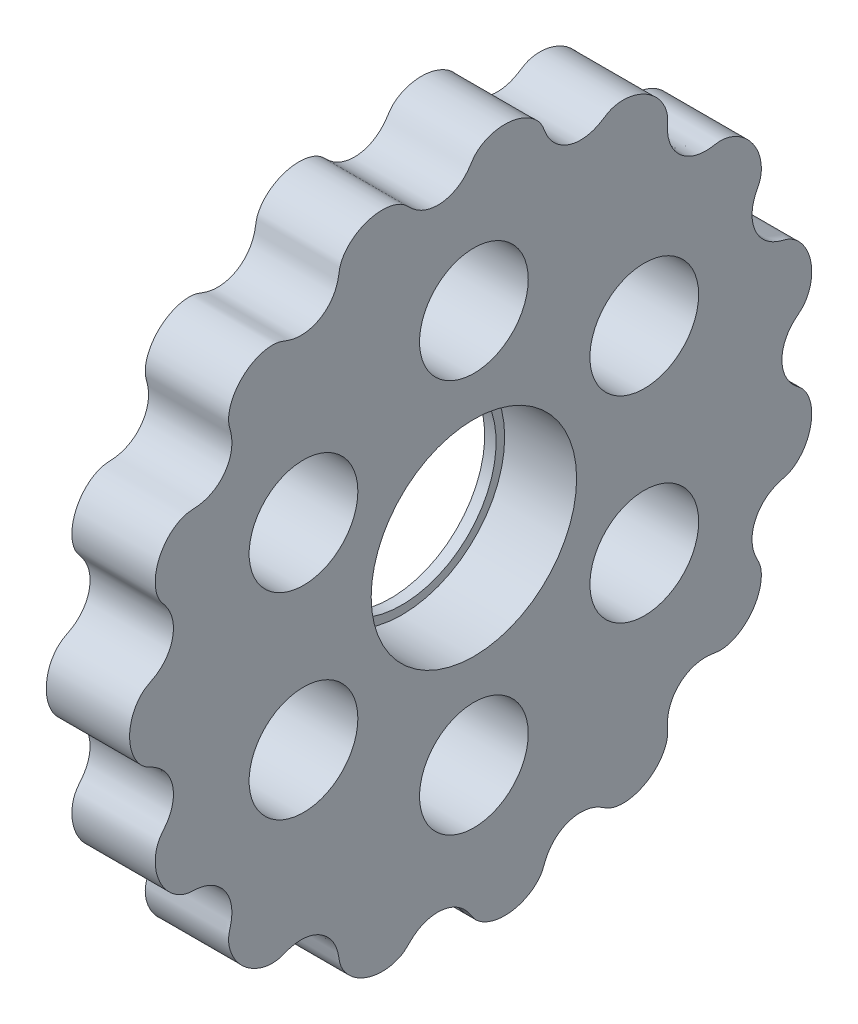
SolidWorks part; units mm, degrees
ref_plane "Front Plane" through (0, 0, 0) normal (0, 0, 1) x (1, 0, 0)
ref_plane "Top Plane" through (0, 0, 0) normal (0, 1, 0) x (1, 0, 0)
ref_plane "Right Plane" through (0, 0, 0) normal (1, 0, 0) x (0, 0, -1)
sketch "Sketch2" plane through (0, 0, 0) normal (0, 0, 1) x (1, 0, 0)
  line L0 (0, 0) -> (58.591, 0) construction
  line L2 (0, 0) -> (18.4, 0)
  line L3 (0, 0) -> (0, 2.5)
  line L4 (0, 2.5) -> (18.4, 2.5)
  line L5 (18.4, 0) -> (18.4, 2.5)
  line L6 (6.0094, 2.5) -> (6.0094, 6)
  line L11 (6.0094, 6) -> (9.9794, 6)
  line L16 (12.9794, 6) -> (12.9794, 3)
  line L17 (12.9794, 3) -> (13.6398, 3)
  line L18 (13.6398, 3) -> (13.6398, 2.5)
  line L19 (13.6398, 2.5) -> (6.0094, 2.5)
  line L22 (13.6398, 2.5) -> (16.1198, 2.5)
  line L23 (13.6398, 2.5) -> (13.6398, 4)
  line L24 (13.6398, 4) -> (16.1198, 4)
  line L25 (16.1198, 2.5) -> (16.1198, 4)
  line L27 (6.0094, 6) -> (9.9794, 6)
  line L28 (6.0094, 6) -> (6.0094, 9)
  line L29 (6.0094, 9) -> (9.9794, 9)
  line L30 (9.9794, 6) -> (9.9794, 9)
  line L31 (6.0094, 9) -> (6.0094, 8.25)
  line L32 (6.0094, 8.25) -> (5.0094, 8.25)
  line L33 (8.6609, 22.001) -> (8.6609, 12.476) construction
  line L34 (5.0094, 12.476) -> (12.3124, 12.476)
  line L35 (9.9794, 9) -> (12.3124, 9)
  line L36 (5.0094, 7.9375) -> (1.8344, 7.9375)
  line L37 (5.0094, 8.25) -> (5.0094, 12.476)
  line L38 (5.0094, 7.9375) -> (5.0094, 13.9365)
  line L39 (5.0094, 13.9365) -> (1.8344, 13.9365)
  line L40 (1.8344, 7.9375) -> (1.8344, 13.9365)
  line L41 (5.0094, 22.001) -> (12.3124, 22.001)
  line L42 (5.0094, 22.001) -> (5.0094, 30.1625)
  line L43 (5.0094, 30.1625) -> (12.3124, 30.1625)
  line L44 (12.3124, 22.001) -> (12.3124, 30.1625)
  line L49 (16.6398, 22.001) -> (16.6398, 7.5)
  line L51 (23.0198, 7.5) -> (23.0198, 6.5)
  line L54 (16.1198, 4) -> (13.6398, 4)
  line L56 (18.0398, 7.5) -> (23.0198, 7.5)
  line L57 (13.3124, 22.001) -> (16.6398, 22.001)
  line L58 (16.1198, 3.5) -> (20.0198, 3.5)
  line L59 (29.9098, 14) -> (26.9098, 11)
  line L60 (4.0094, 31.75) -> (18.0398, 31.75)
  line L61 (18.0398, 7.5) -> (23.0198, 7.5)
  line L62 (18.0398, 7.5) -> (18.0398, 12)
  line L63 (18.0398, 12) -> (23.0198, 12)
  line L64 (23.0198, 7.5) -> (23.0198, 12)
  line L65 (18.0398, 31.75) -> (18.0398, 12)
  line L66 (23.0198, 11) -> (26.9098, 11)
  line L67 (34.8098, 23) -> (31.3098, 19.5)
  line L68 (35.8098, 31) -> (38.7998, 33.99)
  line L69 (29.9098, 14) -> (29.9098, 15)
  line L70 (29.9098, 15) -> (22.9398, 15)
  line L71 (22.9398, 15) -> (21.0398, 15)
  line L72 (18.0398, 7.5) -> (16.6398, 7.5)
  line L73 (21.0398, 15) -> (21.0398, 43)
  line L74 (19.5798, 40) -> (9.6198, 40)
  line L75 (9.6198, 40) -> (4.0094, 40)
  line L76 (21.0398, 43) -> (19.5798, 43)
  line L77 (22.9398, 15) -> (29.9098, 15)
  line L78 (22.9398, 15) -> (22.9398, 21)
  line L79 (22.9398, 21) -> (29.9098, 21)
  line L80 (29.9098, 15) -> (29.9098, 21)
  line L81 (9.6198, 40) -> (19.5798, 40)
  line L82 (9.6198, 40) -> (9.6198, 50)
  line L83 (9.6198, 50) -> (19.5798, 50)
  line L84 (19.5798, 40) -> (19.5798, 50)
  line L85 (4.0094, 40) -> (4.0094, 31.75)
  line L86 (12.9794, 3) -> (12.9794, 2.5)
  line L87 (31.3098, 19.5) -> (29.9098, 19.5)
  line L88 (21.4694, 63.5) -> (21.4694, 51.308)
  line L89 (21.4694, 63.5) -> (25.9398, 63.5)
  line L90 (25.9398, 63.5) -> (25.9398, 25)
  line L91 (27.8398, 25) -> (25.9398, 25)
  line L92 (9.6198, 48) -> (8.1598, 48)
  line L93 (8.1598, 48) -> (8.1598, 53.476)
  line L94 (8.1598, 53.476) -> (19.5798, 53.476)
  line L95 (19.5798, 53.476) -> (19.5798, 50)
  line L96 (13.8698, 63.001) -> (13.8698, 53.476) construction
  line L97 (8.1598, 63.001) -> (19.5798, 63.001)
  line L98 (8.1598, 63.001) -> (8.1598, 68.2625)
  line L99 (8.1598, 68.2625) -> (19.5798, 68.2625)
  line L100 (19.5798, 63.001) -> (19.5798, 68.2625)
  line L101 (12.9794, 6) -> (11.9794, 6)
  line L102 (8.1598, 44.825) -> (4.9848, 44.825)
  line L103 (8.1598, 44.825) -> (8.1598, 54.9365)
  line L104 (8.1598, 54.9365) -> (4.9848, 54.9365)
  line L106 (9.9794, 6) -> (10.8794, 6)
  line L107 (27.8398, 25) -> (34.8098, 25)
  line L108 (34.8098, 25) -> (34.8098, 23)
  line L109 (0, 0) -> (-2, 0)
  line L110 (0, 0) -> (0, 11)
  line L111 (27.8398, 25) -> (34.8098, 25)
  line L112 (27.8398, 25) -> (27.8398, 32.5)
  line L113 (27.8398, 32.5) -> (34.8098, 32.5)
  line L114 (34.8098, 25) -> (34.8098, 32.5)
  line L115 (35.8098, 31) -> (34.8098, 31)
  line L116 (27.8398, 32.5) -> (27.8398, 64.5)
  line L117 (20.5373, 74.025) -> (6.2023, 74.025)
  line L118 (6.2023, 74.025) -> (6.2023, 76.2)
  line L119 (38.7998, 47.29) -> (30.8398, 55.25)
  line L120 (0, 11) -> (-2, 11)
  line L121 (38.7998, 43.815) -> (30.8623, 43.815)
  line L123 (-4.8152, 69.85) -> (1.5348, 76.2)
  line L124 (38.7998, 47.29) -> (38.7998, 33.99)
  line L125 (-2, 0) -> (-2, 11)
  line L126 (38.7998, 37.465) -> (30.8623, 37.465)
  line L127 (30.8623, 43.815) -> (30.8623, 37.465)
  line L128 (6.0094, 2.5) -> (6.0094, 0)
  line L129 (-0.0152, 63.5) -> (-0.0152, 30)
  line L132 (4.9848, 63.5) -> (-0.0152, 63.5)
  line L136 (-1.8152, 30) -> (-11.7752, 30)
  line L138 (-13.7752, 25.4) -> (-2, 25.4)
  line L139 (-2, 25.4) -> (-2, 11.5)
  line L140 (27.8398, 64.5) -> (20.5373, 64.5)
  line L141 (-1.8152, 30) -> (-11.7752, 30)
  line L142 (-1.8152, 30) -> (-1.8152, 39)
  line L143 (-1.8152, 39) -> (-11.7752, 39)
  line L144 (-11.7752, 30) -> (-11.7752, 39)
  line L145 (20.5373, 64.5) -> (20.5373, 74.025)
  line L146 (-12.7752, 37) -> (-12.7752, 47.29)
  line L147 (-12.7752, 37) -> (-11.7752, 37)
  line L148 (30.8398, 55.25) -> (30.8398, 76.2)
  line L149 (11.9794, 6) -> (11.9794, 5.45)
  line L154 (-2, 11.5) -> (0.5, 11.5)
  line L155 (4.9848, 60.6197) -> (24.0348, 60.6197)
  line L160 (4.9848, 60.6197) -> (4.9848, 55.8572)
  line L161 (4.9848, 55.8572) -> (24.0348, 55.8572)
  line L166 (24.0348, 60.6197) -> (24.0348, 55.8572)
  line L167 (4.9848, 60.6197) -> (24.0348, 55.8572) construction
  line L172 (4.9848, 55.8572) -> (24.0348, 60.6197) construction
  line L173 (24.0348, 62.2072) -> (25.9398, 62.2072)
  line L174 (11.9794, 5.45) -> (10.8794, 5.45)
  line L175 (10.8794, 6) -> (10.8794, 5.45)
  line L176 (24.0348, 62.2072) -> (24.0348, 54.2697)
  line L177 (24.0348, 54.2697) -> (25.9398, 54.2697)
  line L178 (25.9398, 62.2072) -> (25.9398, 54.2697)
  line L179 (24.0348, 62.2072) -> (25.9398, 54.2697) construction
  line L180 (24.0348, 54.2697) -> (25.9398, 62.2072) construction
  line L181 (3, 19.6197) -> (15.7, 19.6197)
  line L182 (3, 19.6197) -> (3, 14.8572)
  line L183 (3, 14.8572) -> (15.7, 14.8572)
  line L184 (15.7, 19.6197) -> (15.7, 14.8572)
  line L185 (3, 19.6197) -> (15.7, 14.8572) construction
  line L186 (3, 14.8572) -> (15.7, 19.6197) construction
  line L187 (15.7, 21.2072) -> (16.6398, 21.2072)
  line L188 (15.7, 21.2072) -> (15.7, 13.2697)
  line L189 (15.7, 13.2697) -> (16.6398, 13.2697)
  line L190 (16.6398, 21.2072) -> (16.6398, 13.2697)
  line L191 (15.7, 21.2072) -> (16.6398, 13.2697) construction
  line L192 (15.7, 13.2697) -> (16.6398, 21.2072) construction
  line L193 (0.5, 11.5) -> (0.5, 6.9375)
  line L194 (0.5, 6.9375) -> (1.8344, 6.9375)
  line L195 (23.0198, 6.5) -> (20.0198, 3.5)
  line L196 (4.9848, 63.5) -> (4.9848, 54.9365)
  line L197 (3, 43.825) -> (4.9848, 43.825)
  line L198 (1.8344, 6.9375) -> (1.8344, 7.9375)
  line L199 (6.0094, 0) -> (12.9794, 0)
  line L200 (12.9794, 0) -> (12.9794, 2.5)
  line L201 (18.0398, 31.75) -> (18.0398, 35.875)
  line L202 (18.0398, 35.875) -> (21.0398, 35.875)
  line L203 (30.8398, 76.2) -> (6.2023, 76.2)
  line L204 (2.7573, 69.85) -> (7.2023, 69.85) construction
  line L205 (7.2023, 67.4688) -> (26.2523, 67.4688)
  line L206 (7.2023, 74.025) -> (7.2023, 64.5)
  line L207 (7.2023, 64.5) -> (-1.8152, 64.5)
  line L208 (-1.8152, 64.5) -> (-1.8152, 39)
  line L209 (-12.7752, 47.29) -> (-4.8152, 55.25)
  line L210 (-4.8152, 55.25) -> (-4.8152, 69.85)
  line L211 (7.2023, 67.4688) -> (7.2023, 72.2312)
  line L212 (7.2023, 72.2312) -> (26.2523, 72.2313)
  line L213 (26.2523, 67.4688) -> (26.2523, 72.2313)
  line L214 (26.2523, 73.8187) -> (30.8398, 73.8187)
  line L215 (26.2523, 73.8187) -> (26.2523, 65.8813)
  line L216 (26.2523, 65.8813) -> (30.8398, 65.8813)
  line L217 (30.8398, 73.8187) -> (30.8398, 65.8813)
  line L218 (2.7573, 72.2313) -> (24.9823, 72.2313)
  line L219 (2.7573, 72.2313) -> (2.7573, 67.4687)
  line L220 (2.7573, 67.4687) -> (24.9823, 67.4687)
  line L221 (24.9823, 72.2313) -> (24.9823, 67.4687)
  line L222 (24.9823, 69.85) -> (20.5373, 69.85) construction
  line L223 (21.4694, 51.308) -> (22.9398, 51.308)
  line L224 (22.9398, 51.308) -> (22.9398, 21)
  line L225 (13.6398, 4) -> (13.6398, 12.2697)
  line L226 (13.6398, 12.2697) -> (13.3124, 12.2697)
  line L227 (13.3124, 12.2697) -> (13.3124, 22.001)
  line L228 (12.3124, 9) -> (12.3124, 12.476)
  line L229 (-1.8152, 30) -> (-0.0152, 30)
  line L230 (8.1598, 65.6317) -> (2.7573, 65.6317) construction
  line L231 (19.5798, 65.6317) -> (24.9823, 65.6317) construction
  line L232 (1.5348, 76.2) -> (6.2023, 76.2)
  line L233 (-11.7752, 30) -> (-13.7752, 30)
  line L234 (-13.7752, 30) -> (-13.7752, 25.4)
  line L235 (3, 13.9365) -> (3, 43.825)
  line L236 (4.9848, 54.9365) -> (4.9848, 44.825)
  line L237 (4.9848, 43.825) -> (4.9848, 44.825)
  circle A0 centre (26.8898, 25.95) radius 0.95
  circle A1 centre (21.9898, 15.95) radius 0.95
  circle A2 centre (17.3398, 8.2) radius 0.7
  circle A3 centre (10.4294, 6.45) radius 0.45
  circle A4 centre (-0.9152, 30.9) radius 0.9
  point P7 (24.9873, 58.2385)
  point P131 (16.1699, 17.2385)
  point P135 (14.5098, 58.2385)
  point P146 (9.35, 17.2385)
sketch "Sketch3" plane through (0, 0, 0) normal (1, 0, 0) x (0, 0, -1)
  line L0 (0, 0) -> (0, 69.85) construction
  line L1 (0, 0) -> (13.6271, 68.5079) construction
  line L2 (0, 0) -> (0, 58.2385) construction
  line L3 (0, 0) -> (50.436, 29.1192) construction
  line L4 (0, 0) -> (0, 31.75) construction
  line L5 (0, 0) -> (12.1502, 29.3332) construction
  line L6 (0, 0) -> (0, 17.2385) construction
  line L7 (0, 0) -> (14.929, 8.6192) construction
  line L8 (0, 0) -> (0, 58.2385) construction
  line L9 (0, 0) -> (50.436, 29.1192) construction
  line L10 (0, 0) -> (5.9583, 29.9542) construction
  line L11 (0, 0) -> (16.9677, 25.394) construction
  circle A0 centre (0, 0) radius 69.85 construction
  circle A1 centre (0, 0) radius 58.2385 construction
  circle A2 centre (0, 0) radius 31.75 construction
  circle A3 centre (0, 0) radius 17.2385 construction
  circle A4 centre (0, 69.85) radius 3.175
  circle A5 centre (0, 58.2385) radius 4.7625
  circle A6 centre (0, 31.75) radius 3.175
  circle A7 centre (0, 17.2385) radius 4.7625
  circle A8 centre (13.6271, 68.5079) radius 3.175
  circle A9 centre (26.7304, 64.533) radius 3.175
  circle A10 centre (38.8066, 58.0782) radius 3.175
  circle A11 centre (49.3914, 49.3914) radius 3.175
  circle A12 centre (58.0782, 38.8066) radius 3.175
  circle A13 centre (64.533, 26.7304) radius 3.175
  circle A14 centre (68.5079, 13.6271) radius 3.175
  circle A15 centre (69.85, 0) radius 3.175
  circle A16 centre (68.5079, -13.6271) radius 3.175
  circle A17 centre (64.533, -26.7304) radius 3.175
  circle A18 centre (58.0782, -38.8066) radius 3.175
  circle A19 centre (49.3914, -49.3914) radius 3.175
  circle A20 centre (38.8066, -58.0782) radius 3.175
  circle A21 centre (26.7304, -64.533) radius 3.175
  circle A22 centre (13.6271, -68.5079) radius 3.175
  circle A23 centre (0, -69.85) radius 3.175
  circle A24 centre (-13.6271, -68.5079) radius 3.175
  circle A25 centre (-26.7304, -64.533) radius 3.175
  circle A26 centre (-38.8066, -58.0782) radius 3.175
  circle A27 centre (-49.3914, -49.3914) radius 3.175
  circle A28 centre (-58.0782, -38.8066) radius 3.175
  circle A29 centre (-64.533, -26.7304) radius 3.175
  circle A30 centre (-68.5079, -13.6271) radius 3.175
  circle A31 centre (-69.85, 0) radius 3.175
  circle A32 centre (-68.5079, 13.6271) radius 3.175
  circle A33 centre (-64.533, 26.7304) radius 3.175
  circle A34 centre (-58.0782, 38.8066) radius 3.175
  circle A35 centre (-49.3914, 49.3914) radius 3.175
  circle A36 centre (-38.8066, 58.0782) radius 3.175
  circle A37 centre (-26.7304, 64.533) radius 3.175
  circle A38 centre (-13.6271, 68.5079) radius 3.175
  circle A47 centre (50.436, 29.1192) radius 4.7625
  circle A48 centre (50.436, -29.1192) radius 4.7625
  circle A49 centre (0, -58.2385) radius 4.7625
  circle A50 centre (-50.436, -29.1192) radius 4.7625
  circle A51 centre (-50.436, 29.1192) radius 4.7625
  circle A58 centre (12.1502, 29.3332) radius 3.175
  circle A59 centre (22.4506, 22.4506) radius 3.175
  circle A60 centre (29.3332, 12.1502) radius 3.175
  circle A61 centre (31.75, 0) radius 3.175
  circle A62 centre (29.3332, -12.1502) radius 3.175
  circle A63 centre (22.4506, -22.4506) radius 3.175
  circle A64 centre (12.1502, -29.3332) radius 3.175
  circle A65 centre (0, -31.75) radius 3.175
  circle A66 centre (-12.1502, -29.3332) radius 3.175
  circle A67 centre (-22.4506, -22.4506) radius 3.175
  circle A68 centre (-29.3332, -12.1502) radius 3.175
  circle A69 centre (-31.75, 0) radius 3.175
  circle A70 centre (-29.3332, 12.1502) radius 3.175
  circle A71 centre (-22.4506, 22.4506) radius 3.175
  circle A72 centre (14.929, 8.6192) radius 4.7625
  circle A73 centre (14.929, -8.6192) radius 4.7625
  circle A74 centre (0, -17.2385) radius 4.7625
  circle A75 centre (-14.929, -8.6192) radius 4.7625
  circle A76 centre (-14.929, 8.6192) radius 4.7625
  circle A77 centre (0, 0) radius 50
  circle A78 centre (0, 0) radius 9
  circle A79 centre (-12.1502, 29.3332) radius 3.175
  circle A80 centre (0, 0) radius 76.2
  circle A81 centre (0, 0) radius 74.025
  circle A82 centre (0, 69.85) radius 3.9687
  circle A83 centre (49.3914, 49.3914) radius 3.9687
  circle A84 centre (69.85, 0) radius 3.9688
  circle A85 centre (49.3914, -49.3914) radius 3.9687
  circle A86 centre (0, -69.85) radius 3.9687
  circle A87 centre (-49.3914, -49.3914) radius 3.9687
  circle A88 centre (-69.85, 0) radius 3.9688
  circle A89 centre (-49.3914, 49.3914) radius 3.9687
  circle A90 centre (0, 69.85) radius 2.3812
  circle A91 centre (13.6271, 68.5079) radius 2.3812
  circle A92 centre (26.7304, 64.533) radius 2.3813
  circle A93 centre (38.8066, 58.0782) radius 2.3812
  circle A94 centre (49.3914, 49.3914) radius 2.3812
  circle A95 centre (58.0782, 38.8066) radius 2.3812
  circle A96 centre (64.533, 26.7304) radius 2.3813
  circle A97 centre (68.5079, 13.6271) radius 2.3813
  circle A98 centre (69.85, 0) radius 2.3813
  circle A99 centre (68.5079, -13.6271) radius 2.3813
  circle A100 centre (64.533, -26.7304) radius 2.3813
  circle A101 centre (58.0782, -38.8066) radius 2.3812
  circle A102 centre (49.3914, -49.3914) radius 2.3812
  circle A103 centre (38.8066, -58.0782) radius 2.3812
  circle A104 centre (26.7304, -64.533) radius 2.3813
  circle A105 centre (13.6271, -68.5079) radius 2.3812
  circle A106 centre (0, -69.85) radius 2.3812
  circle A107 centre (-13.6271, -68.5079) radius 2.3812
  circle A108 centre (-26.7304, -64.533) radius 2.3813
  circle A109 centre (-38.8066, -58.0782) radius 2.3812
  circle A110 centre (-49.3914, -49.3914) radius 2.3812
  circle A111 centre (-58.0782, -38.8066) radius 2.3812
  circle A112 centre (-64.533, -26.7304) radius 2.3812
  arc A113 (3.0399, 30.8338) -> (8.9911, 29.65) centre (5.9583, 29.9542) cw
  arc A114 (14.6081, 27.3234) -> (19.6532, 23.9523) centre (16.9677, 25.394) cw
  arc A115 (23.9523, 19.6532) -> (27.3234, 14.6081) centre (25.394, 16.9677) cw
  arc A116 (29.65, 8.9911) -> (30.8338, 3.0399) centre (29.9542, 5.9583) cw
  arc A117 (30.8338, -3.0399) -> (29.65, -8.9911) centre (29.9542, -5.9583) cw
  arc A118 (27.3234, -14.6081) -> (23.9523, -19.6532) centre (25.394, -16.9677) cw
  arc A119 (19.6532, -23.9523) -> (14.6081, -27.3234) centre (16.9677, -25.394) cw
  arc A120 (8.9911, -29.65) -> (3.0399, -30.8338) centre (5.9583, -29.9542) cw
  arc A121 (-3.0399, -30.8338) -> (-8.9911, -29.65) centre (-5.9583, -29.9542) cw
  arc A122 (-14.6081, -27.3234) -> (-19.6532, -23.9523) centre (-16.9677, -25.394) cw
  arc A123 (-23.9523, -19.6532) -> (-27.3234, -14.6081) centre (-25.394, -16.9677) cw
  arc A124 (-29.65, -8.9911) -> (-30.8338, -3.0399) centre (-29.9542, -5.9583) cw
  arc A125 (-30.8338, 3.0399) -> (-29.65, 8.9911) centre (-29.9542, 5.9583) cw
  arc A126 (-27.3234, 14.6081) -> (-23.9523, 19.6532) centre (-25.394, 16.9677) cw
  arc A127 (-19.6532, 23.9523) -> (-14.6081, 27.3234) centre (-16.9677, 25.394) cw
  arc A128 (-8.9911, 29.65) -> (-3.0399, 30.8338) centre (-5.9583, 29.9542) cw
  arc A129 (26.9875, 0) -> (26.9932, 0.1932) centre (30.2705, 0) cw
  arc A130 (65.0988, 0.2771) -> (65.0875, 0) centre (68.4964, 0) ccw
  circle A131 centre (1.5875, 0) radius 40
  circle A132 centre (1.5875, 0) radius 2.5
  circle A133 centre (1.5875, 0) radius 3
  circle A134 centre (1.5875, 0) radius 43
  circle A135 centre (-68.5079, -13.6271) radius 2.3813
  circle A136 centre (-69.85, 0) radius 2.3813
  circle A137 centre (-68.5079, 13.6271) radius 2.3813
  circle A138 centre (-64.533, 26.7304) radius 2.3812
  circle A139 centre (-58.0782, 38.8066) radius 2.3812
  circle A140 centre (-49.3914, 49.3914) radius 2.3812
  circle A141 centre (-38.8066, 58.0782) radius 2.3812
  circle A142 centre (-26.7304, 64.533) radius 2.3813
  circle A143 centre (-13.6271, 68.5079) radius 2.3812
  circle A144 centre (0, 58.2385) radius 2.3812
  circle A145 centre (0, 58.2385) radius 3.9688
  circle A146 centre (50.436, 29.1192) radius 3.9688
  circle A147 centre (50.436, 29.1192) radius 2.3813
  circle A148 centre (50.436, -29.1192) radius 3.9687
  circle A149 centre (50.436, -29.1192) radius 2.3812
  circle A150 centre (0, -58.2385) radius 3.9687
  circle A151 centre (0, -58.2385) radius 2.3812
  circle A152 centre (-50.436, -29.1192) radius 3.9687
  circle A153 centre (-50.436, -29.1192) radius 2.3812
  circle A154 centre (-50.436, 29.1192) radius 3.9687
  circle A155 centre (-50.436, 29.1192) radius 2.3812
  spline S1 degree 4 number of poles 499 (26.9875, 0) -> (26.9932, 0.1932)
  spline S3 degree 4 number of poles 617 (65.0875, 0) -> (65.0988, 0.2771)
  point P116 (0, 0)
  point P225 (0, 0)
sketch "Sketch4" plane through (0, 0, 0) normal (0, 0, 1) x (1, 0, 0)
  line L0 (6.0094, 9) -> (9.9794, 9) construction
  line L1 (9.9794, 9) -> (12.3124, 9) construction
  line L2 (12.3124, 9) -> (12.3124, 12.476) construction
  line L3 (6.0094, 9) -> (9.9794, 9)
  line L4 (6.0094, 6) -> (6.0094, 9) construction
  line L7 (5.0094, 12.476) -> (12.3124, 12.476) construction
  line L8 (5.0094, 8.25) -> (5.0094, 12.476) construction
  line L9 (6.0094, 8.25) -> (5.0094, 8.25) construction
  line L14 (6.0094, 8.25) -> (6.0094, 9)
  line L17 (5.0094, 12.476) -> (12.3124, 12.476)
  line L18 (5.0094, 8.25) -> (5.0094, 12.476)
  line L19 (6.0094, 8.25) -> (5.0094, 8.25)
  line L20 (9.9794, 9) -> (12.3124, 9)
  line L21 (12.3124, 9) -> (12.3124, 12.476)
revolve "Revolve1" add sketch "Sketch4" angle 360 about L0
sketch "Sketch6" plane through (0, 0, 0) normal (1, 0, 0) x (0, 0, -1)
  circle A0 centre (-14.929, -8.6192) radius 4.7625 construction
  circle A1 centre (0, -17.2385) radius 4.7625 construction
  circle A2 centre (14.929, -8.6192) radius 4.7625 construction
  circle A3 centre (14.929, 8.6192) radius 4.7625 construction
  circle A4 centre (0, 17.2385) radius 4.7625 construction
  circle A5 centre (-14.929, 8.6192) radius 4.7625 construction
  circle A6 centre (-14.929, -8.6192) radius 4.7625
  circle A7 centre (0, -17.2385) radius 4.7625
  circle A8 centre (14.929, -8.6192) radius 4.7625
  circle A9 centre (14.929, 8.6192) radius 4.7625
  circle A10 centre (0, 17.2385) radius 4.7625
  circle A11 centre (-14.929, 8.6192) radius 4.7625
  circle A12 centre (0, 0) radius 9 construction
  circle A13 centre (0, 0) radius 9
  arc A14 (26.9932, 0.1932) -> (26.9875, 0) centre (30.2705, 0) ccw construction
  arc A15 (26.9932, 0.1932) -> (26.9875, 0) centre (30.2705, 0) ccw
  spline S0 degree 4 number of poles 499 (26.9875, 0) -> (26.9932, 0.1932) construction
  spline S1 degree 4 number of poles 499 (26.9875, 0) -> (26.9932, 0.1932)
extrude "Boss-Extrude1" add sketch "Sketch6" along normal up to vertex (12.3124 mm away) from vertex contours S1 A15 A13 A11 A10 A9 A8 A7 A6 region at (0, 0.1216, -26.1422) up to point (12.3124, 12.476, 0) starting at point (5.0094, 12.476, 0)
